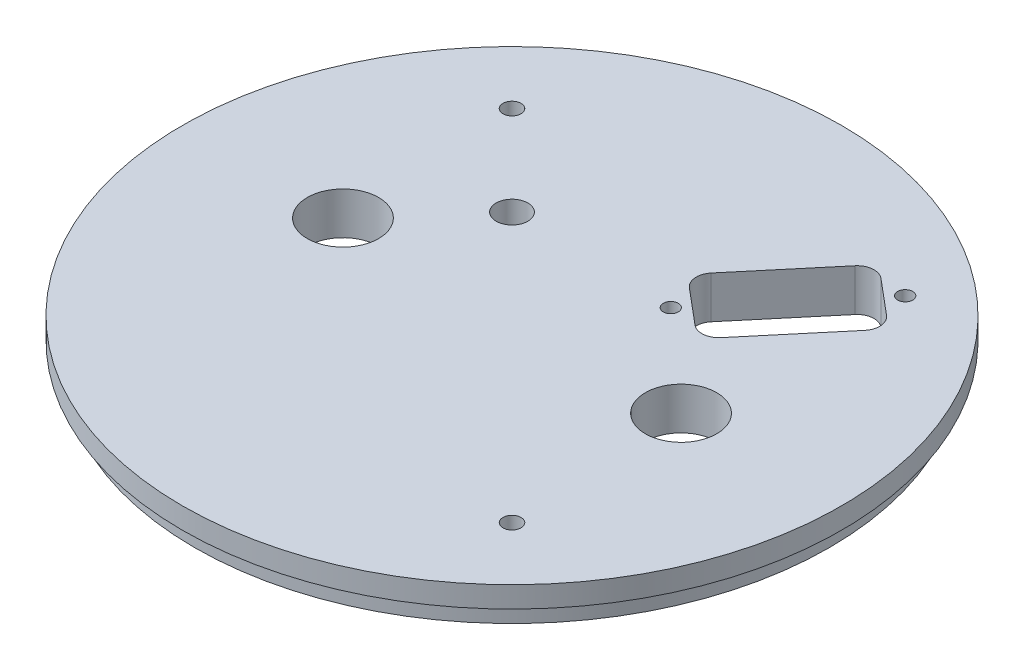
SolidWorks part; units mm, degrees
material "6061-T6 (SS)"
ref_plane "Front Plane" through (0, 0, 0) normal (0, 0, 1) x (1, 0, 0)
ref_plane "Top Plane" through (0, 0, 0) normal (0, 1, 0) x (1, 0, 0)
ref_plane "Right Plane" through (0, 0, 0) normal (1, 0, 0) x (0, 0, -1)
sketch "Sketch1" plane through (0, 0, 0) normal (0, 1, 0) x (1, 0, 0)
  line L0 (0, -49.5173) -> (0, 49.5173) construction
  line L1 (-49.5173, 0) -> (49.5173, 0) construction
  line L2 (-26.9408, 26.9408) -> (0, 0) construction
  line L3 (0, 56.7387) -> (0, 29.6936) construction
  line L4 (3.6407, 56.7387) -> (3.6407, 29.6936) construction
  line L5 (-3.6407, 56.7387) -> (-3.6407, 29.6936) construction
  line L6 (0, -56.7387) -> (0, -29.6936) construction
  line L7 (3.6407, -56.7387) -> (3.6407, -29.6936) construction
  line L8 (-3.6407, -56.7387) -> (-3.6407, -29.6936) construction
  line L9 (-35.014, -35.014) -> (54.3236, 54.3236) construction
  circle A0 centre (0, 0) radius 49.5173
  circle A1 centre (0, 0) radius 3.175 construction
  circle A2 centre (25.4, 0) radius 5.3578
  circle A3 centre (-25.4, 0) radius 5.3578
  circle A4 centre (-26.9408, 26.9408) radius 1.3589
  arc A6 (3.6407, 56.7387) -> (-3.6407, 56.7387) centre (0, 56.7387) ccw construction
  arc A7 (-3.6407, 29.6936) -> (3.6407, 29.6936) centre (0, 29.6936) ccw construction
  arc A8 (3.6407, -56.7387) -> (-3.6407, -56.7387) centre (0, -56.7387) cw construction
  arc A9 (-3.6407, -29.6936) -> (3.6407, -29.6936) centre (0, -29.6936) cw construction
  circle A10 centre (26.9408, -26.9408) radius 1.3589
  circle A11 centre (-13.4704, 13.4704) radius 2.3813
  circle A12 centre (13.4704, -13.4704) radius 2.3813 construction
  point P16 (0, 43.2162)
  point P19 (0, 0)
  point P26 (0, -43.2162)
  dimension "D1" = 99.0346
  dimension "D2" = 6.35
  dimension "D3" = 10.7156
  dimension "D5" = 2.7178
  dimension "D8" = 4.7625
  dimension "D6" = 38.1
  dimension "D7" = 45
  dimension "D4" = 45
  dimension "D9" = 25.4
extrude "Boss-Extrude1" add sketch "Sketch1" along normal blind 6.35
sketch "Sketch2" plane through (0, 0, 0) normal (0, -1, 0) x (1, 0, 0)
  circle A0 centre (0, 0) radius 49.5173
  circle A1 centre (0, 0) radius 47.6885
  dimension "D1" = 99.0346
  dimension "D2" = 95.377
extrude "Cut-Extrude1" cut sketch "Sketch2" against normal blind 3.175
sketch "Sketch3" plane through (0, 6.35, 0) normal (0, 1, 0) x (1, 0, 0)
  line L0 (0, 49.5173) -> (0, -49.5173) construction
  line L1 (-49.5173, 0) -> (49.5173, 0) construction
  line L2 (0, 34.925) -> (0, 13.335) construction
  line L3 (3.2385, 34.925) -> (3.2385, 13.335)
  line L4 (-3.2385, 34.925) -> (-3.2385, 13.335)
  line L5 (0, -34.925) -> (0, -13.335) construction
  line L6 (3.2385, -34.925) -> (3.2385, -13.335)
  line L7 (-3.2385, -34.925) -> (-3.2385, -13.335)
  circle A0 centre (0, 0) radius 49.5173 construction
  arc A1 (3.2385, 34.925) -> (-3.2385, 34.925) centre (0, 34.925) ccw
  arc A2 (-3.2385, 13.335) -> (3.2385, 13.335) centre (0, 13.335) ccw
  arc A3 (3.2385, -34.925) -> (-3.2385, -34.925) centre (0, -34.925) cw
  arc A4 (-3.2385, -13.335) -> (3.2385, -13.335) centre (0, -13.335) cw
  point P7 (0, 13.335)
  point P8 (0, 34.925)
  point P12 (0, 24.13)
  point P20 (0, -24.13)
  point P25 (0, -34.925)
  point P26 (0, -13.335)
  dimension "D1" = 13.335
  dimension "D2" = 34.925
  dimension "D3" = 6.477
extrude "Cut-Extrude2" cut sketch "Sketch3" against normal blind 3.556 from offset 5.969 offset against normal yes
hole_wizard "Tap Drill for #4-40 Tap1" positions "Sketch5" profile "Sketch6" hole size "#4-40" standard "ANSI Inch" end condition through all
sketch "Sketch5" plane through (0, 6.35, 0) normal (0, 1, 0) x (1, 0, 0)
  line L0 (0, 0) -> (53.6567, 63.9455) construction
  line L2 (0, 0) -> (25.4, 0) construction
  point P0 (10.8845, 12.9717)
  point P2 (26.9542, 32.1228)
  dimension "D1" = 50
  dimension "D2" = 25
  dimension "D3" = 16.9333
sketch "Sketch6" plane through (10.8845, 6.35, -12.9717) normal (1, 0, 0) x (0, 0, 1)
  line L0 (0, 0) -> (0, 6.35)
  line L1 (0, 6.35) -> (1.1303, 6.35)
  line L2 (1.1303, 6.35) -> (1.1303, 0)
  line L5 (1.1303, 0) -> (0, 0)
  line L11 (0, -6.35) -> (0, 107.95) construction
  dimension "Thru Hole Dia." = 2.2606
  dimension "Thru Hole Depth" = 6.35
sketch "Sketch4" plane through (0, 6.35, 0) normal (0, 1, 0) x (1, 0, 0)
  line L0 (9.7272, 16.927) -> (14.9807, 12.5187)
  line L1 (9.4141, 20.5054) -> (19.2796, 32.2627)
  line L2 (18.5591, 12.8318) -> (28.4247, 24.5891)
  line L3 (22.858, 32.5757) -> (28.1116, 28.1675)
  line L4 (0, 0) -> (26.9542, 32.1228) construction
  circle A1 centre (10.8845, 12.9717) radius 1.1303 construction
  arc A2 (19.2796, 32.2627) -> (22.858, 32.5757) centre (21.2254, 30.63) cw
  arc A3 (28.4247, 24.5891) -> (28.1116, 28.1675) centre (26.4789, 26.2217) ccw
  arc A4 (14.9807, 12.5187) -> (18.5591, 12.8318) centre (16.6134, 14.4645) ccw
  arc A5 (9.4141, 20.5054) -> (9.7272, 16.927) centre (11.3599, 18.8727) ccw
  point P11 (12.3539, 14.7229)
  dimension "D4" = 2.54
  dimension "D1" = 2.286
  dimension "D2" = 2.286
  dimension "D3" = 11.938
extrude "Cut-Extrude3" cut sketch "Sketch4" against normal through all
equation "\"leadDist\"= \"Lead_Screw_Dist\""
equation "\"Lead_Screw_Dist\"= 2in"
equation "\"D9@Sketch1\"=\"Lead_Screw_Dist\"/2"
equation "\"Lead_Screw_Diam\"= 0.375in"
equation "\"D3@Sketch1\"=\"Lead_Screw_Hole_Diam\""
equation "\"DB9_Hole_Dist\"= 25mm"
equation "\"Airbrakes_Wire_Hole_Dia\"= .25in"
equation "\"Mid_Coupler_Length\"= 13in"
equation "\"D2@Sketch5\"=\"DB9_Hole_Dist\""
equation "\"DB9_Relief_Width\"= 0.47in"
equation "\"DB9_Relief_Hole_Offset\"= 0.09in"
equation "\"D1@Sketch4\"=\"DB9_Relief_Hole_Offset\""
equation "\"D2@Sketch4\"=\"DB9_Relief_Hole_Offset\""
equation "\"D3@Sketch4\"=\"DB9_Relief_Width\""
equation "\"Body_Tube_OD\"= 4.024in"
equation "\"Body_Tube_ID\"= 3.90in"
equation "\"Coupler_OD\"= 3.899in"
equation "\"Coupler_ID\"= 3.755in"
equation "\"Avionics_Bulkhead_Thickness\"= 0.25in"
equation "\"Avionics_Bulkhead_Lip\"= 0.125in"
equation "\"Lead_Screw_Hole_Diam\"= (27/64)*1in"
equation "\"Lead_Screw_Length\"= \"Mid_Coupler_Length\" + 2*0.375in + 2*0.5in"
equation "\"D1@Sketch1\"=\"Coupler_OD\""
equation "\"D1@Sketch2\"=\"Coupler_OD\""
equation "\"D1@Cut-Extrude1\"=\"Avionics_Bulkhead_Lip\""
equation "\"D1@Boss-Extrude1\"=\"Avionics_Bulkhead_Thickness\""
equation "\"D2@Sketch2\"=\"Coupler_ID\""
